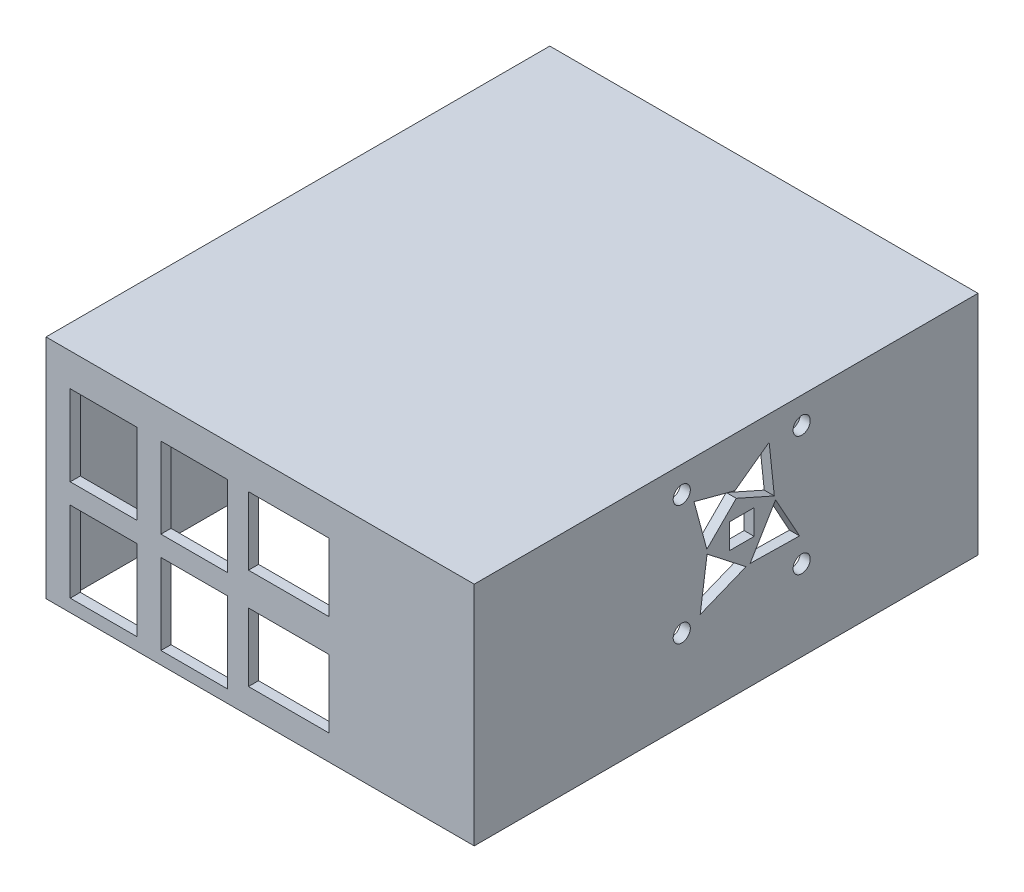
SolidWorks part; units mm, degrees
ref_plane "Front Plane" through (0, 0, 0) normal (0, 0, 1) x (1, 0, 0)
ref_plane "Top Plane" through (0, 0, 0) normal (0, 1, 0) x (1, 0, 0)
ref_plane "Right Plane" through (0, 0, 0) normal (1, 0, 0) x (0, 0, -1)
sketch "Sketch1" plane through (0, 0, 0) normal (0, 1, 0) x (1, 0, 0)
  line L1 (-42.5, -50) -> (42.5, -50)
  line L2 (-42.5, -50) -> (-42.5, 50)
  line L3 (-42.5, 50) -> (42.5, 50)
  line L4 (42.5, -50) -> (42.5, 50)
  line L5 (-42.5, -50) -> (42.5, 50) construction
  line L6 (-42.5, 50) -> (42.5, -50) construction
  point P0 (0, 0)
  dimension "D1" = 100
  dimension "D2" = 85
extrude "Boss-Extrude1" add sketch "Sketch1" along normal blind 45
shell "Shell1" thickness 2 removed face at (0, 0, 0)
sketch "Sketch3" plane through (0, 43, 0) normal (0, -1, 0) x (1, 0, 0)
  line L0 (-36.5, 24.5) -> (12.5, 24.5) construction
  line L1 (12.5, 24.5) -> (12.5, -33.5) construction
  line L2 (12.5, -33.5) -> (-36.5, -33.5) construction
  line L3 (-36.5, -33.5) -> (-36.5, 24.5) construction
  line L5 (-40.5, 48) -> (40.5, 48) construction
  line L6 (-36.5, -4.5) -> (-40.5, -4.5) construction
  line L7 (-40.5, -48) -> (-40.5, 48) construction
  line L8 (12.5, -4.5) -> (40.5, -4.5) construction
  line L9 (40.5, 48) -> (40.5, -48) construction
  circle A0 centre (-36.5, 24.5) radius 2.5
  circle A1 centre (12.5, 24.5) radius 2.5
  circle A2 centre (-36.5, -33.5) radius 2.5
  circle A3 centre (12.5, -33.5) radius 2.5
  dimension "D4" = 5
  dimension "D1" = 58
  dimension "D2" = 49
  dimension "D3" = 23.5
  dimension "D5" = 4
extrude "Boss-Extrude2" add sketch "Sketch3" along normal blind 3
sketch "Sketch4" plane through (0, 40, 0) normal (0, -1, 0) x (1, 0, 0)
  circle A0 centre (12.5, 24.5) radius 1.025
  circle A1 centre (-36.5, 24.5) radius 1.025
  circle A2 centre (-36.5, -33.5) radius 1.025
  circle A3 centre (12.5, -33.5) radius 1.025
  dimension "D1" = 2.05
extrude "Cut-Extrude1" cut sketch "Sketch4" against normal blind 2.7
sketch "Sketch17" plane through (0, 0, 50) normal (0, 0, 1) x (1, 0, 0)
  line L0 (0, 45) -> (0, 0) construction
  line L1 (-42.5, 45) -> (42.5, 45) construction
  line L2 (42.5, 38.5) -> (-42.5, 38.5) construction
  line L3 (-24.44, 22.5) -> (-37.69, 22.5)
  line L4 (-24.44, 22.5) -> (-24.44, 38.5)
  line L5 (-24.44, 38.5) -> (-37.69, 38.5)
  line L6 (-37.69, 22.5) -> (-37.69, 38.5)
  line L7 (-24.44, 22.5) -> (-37.69, 38.5) construction
  line L8 (-24.44, 38.5) -> (-37.69, 22.5) construction
  line L9 (-6.44, 22.5) -> (-19.69, 22.5)
  line L10 (-6.44, 22.5) -> (-6.44, 38.5)
  line L11 (-6.44, 38.5) -> (-19.69, 38.5)
  line L12 (-19.69, 22.5) -> (-19.69, 38.5)
  line L13 (-6.44, 22.5) -> (-19.69, 38.5) construction
  line L14 (-6.44, 38.5) -> (-19.69, 22.5) construction
  line L15 (13.69, 25) -> (-2.31, 25)
  line L16 (13.69, 25) -> (13.69, 38.5)
  line L17 (13.69, 38.5) -> (-2.31, 38.5)
  line L18 (-2.31, 25) -> (-2.31, 38.5)
  line L19 (13.69, 25) -> (-2.31, 38.5) construction
  line L20 (13.69, 38.5) -> (-2.31, 25) construction
  line L21 (42.5, 45) -> (42.5, 0) construction
  line L22 (-42.5, 45) -> (-42.5, 0) construction
  line L23 (13.69, 31.75) -> (42.5, 31.75) construction
  line L24 (-37.69, 30.5) -> (-42.5, 30.5) construction
  point P5 (-31.065, 30.5)
  point P10 (-13.065, 30.5)
  point P15 (5.69, 31.75)
  dimension "D1" = 6.5
  dimension "D2" = 13.5
  dimension "D3" = 16
  dimension "D4" = 16
  dimension "D5" = 13.25
  dimension "D6" = 4.75
  dimension "D7" = 4.13
  dimension "D8" = 4.81
extrude "Cut-Extrude2" cut sketch "Sketch17" against normal up to surface (2 mm away) up to face at (0, 21.5, 48)
pattern_linear "LPattern1" count 2 spacing 20 along (0, -1, 0) of "Cut-Extrude2"
sketch "Sketch18" plane through (42.5, 0, 0) normal (1, 0, 0) x (0, 0, -1)
  line L0 (15, 39.8) -> (-8.8, 39.8) construction
  line L1 (-2.85, 21.95) -> (0.125, 16)
  line L2 (-8.8, 39.8) -> (-8.8, 16) construction
  line L3 (-8.8, 16) -> (15, 16) construction
  line L4 (15, 16) -> (15, 39.8) construction
  line L5 (-50, 45) -> (50, 45) construction
  line L6 (50, 45) -> (50, 0) construction
  line L7 (3.1, 16) -> (3.1, 39.8) construction
  line L8 (3.1, 27.9) -> (-8.8, 27.9) construction
  line L9 (3.1, 27.9) -> (15, 27.9) construction
  line L10 (9.05, 27.9) -> (9.05, 16) construction
  line L11 (9.05, 21.95) -> (3.1, 21.95) construction
  line L12 (9.05, 21.95) -> (15, 21.95) construction
  line L13 (12.025, 16) -> (15, 21.95)
  line L14 (15, 21.95) -> (9.05, 21.95)
  line L15 (9.05, 21.95) -> (12.025, 16)
  line L22 (9.05, 21.95) -> (9.05, 16)
  line L23 (9.05, 16) -> (3.1, 18.975)
  line L24 (3.1, 18.975) -> (9.05, 21.95)
  line L25 (9.05, 21.95) -> (3.1, 21.95)
  line L26 (3.1, 21.95) -> (6.075, 27.9)
  line L27 (6.075, 27.9) -> (9.05, 21.95)
  line L28 (6.075, 21.95) -> (6.075, 27.9) construction
  line L29 (9.05, 18.975) -> (3.1, 18.975) construction
  line L30 (12.025, 16) -> (12.025, 21.95) construction
  line L31 (9.05, 21.95) -> (9.05, 27.9)
  line L32 (9.05, 27.9) -> (9.05, 21.95) construction
  line L33 (9.05, 27.9) -> (15, 24.925)
  line L34 (15, 24.925) -> (9.05, 21.95)
  line L35 (15, 24.925) -> (9.05, 24.925) construction
  line L36 (0.125, 16) -> (3.1, 21.95)
  line L37 (3.1, 21.95) -> (-2.85, 21.95)
  line L38 (0.125, 16) -> (0.125, 21.95) construction
  line L39 (-2.85, 18.975) -> (-8.8, 18.975) construction
  line L40 (-2.85, 21.95) -> (-2.85, 16)
  line L41 (-2.85, 16) -> (-8.8, 18.975)
  line L42 (-8.8, 18.975) -> (-2.85, 21.95)
  line L43 (-5.825, 21.95) -> (-5.825, 27.9) construction
  line L44 (-2.85, 21.95) -> (-8.8, 21.95)
  line L45 (-8.8, 21.95) -> (-5.825, 27.9)
  line L46 (-5.825, 27.9) -> (-2.85, 21.95)
  line L47 (3.1, 24.925) -> (-2.85, 24.925) construction
  line L48 (-2.85, 21.95) -> (-2.85, 27.9)
  line L49 (-2.85, 27.9) -> (3.1, 24.925)
  line L50 (3.1, 24.925) -> (-2.85, 21.95)
  line L51 (-2.85, 33.85) -> (0.125, 27.9)
  line L52 (0.125, 27.9) -> (3.1, 33.85)
  line L53 (3.1, 33.85) -> (-2.85, 33.85)
  line L54 (0.125, 27.9) -> (0.125, 33.85) construction
  line L55 (-2.85, 30.875) -> (-8.8, 30.875) construction
  line L56 (-2.85, 33.85) -> (-2.85, 27.9)
  line L57 (-2.85, 27.9) -> (-8.8, 30.875)
  line L58 (-8.8, 30.875) -> (-2.85, 33.85)
  line L59 (-5.825, 33.85) -> (-5.825, 39.8) construction
  line L60 (-2.85, 33.85) -> (-8.8, 33.85)
  line L61 (-8.8, 33.85) -> (-5.825, 39.8)
  line L62 (-5.825, 39.8) -> (-2.85, 33.85)
  line L63 (3.1, 36.825) -> (-2.85, 36.825) construction
  line L64 (-2.85, 33.85) -> (-2.85, 39.8)
  line L65 (-2.85, 39.8) -> (3.1, 36.825)
  line L66 (3.1, 36.825) -> (-2.85, 33.85)
  line L67 (9.05, 33.85) -> (12.025, 27.9)
  line L68 (12.025, 27.9) -> (15, 33.85)
  line L69 (15, 33.85) -> (9.05, 33.85)
  line L70 (12.025, 27.9) -> (12.025, 33.85) construction
  line L71 (9.05, 30.875) -> (3.1, 30.875) construction
  line L72 (9.05, 33.85) -> (9.05, 27.9)
  line L73 (9.05, 27.9) -> (3.1, 30.875)
  line L74 (3.1, 30.875) -> (9.05, 33.85)
  line L75 (6.075, 33.85) -> (6.075, 39.8) construction
  line L76 (9.05, 33.85) -> (3.1, 33.85)
  line L77 (3.1, 33.85) -> (6.075, 39.8)
  line L78 (6.075, 39.8) -> (9.05, 33.85)
  line L79 (15, 36.825) -> (9.05, 36.825) construction
  line L80 (9.05, 33.85) -> (9.05, 39.8)
  line L81 (9.05, 39.8) -> (15, 36.825)
  line L82 (15, 36.825) -> (9.05, 33.85)
  line L83 (-8.8, 21.95) -> (-8.8, 30.875)
  line L84 (-8.8, 30.875) -> (-8.8, 33.85)
  line L85 (-2.85, 39.8) -> (-5.825, 39.8)
  line L86 (-2.85, 39.8) -> (3.1, 39.8)
  line L87 (3.1, 39.8) -> (6.075, 39.8)
  line L88 (9.05, 39.8) -> (6.075, 39.8)
  line L89 (15, 36.825) -> (15, 33.85)
  line L90 (15, 27.9) -> (15, 33.85)
  line L91 (15, 21.95) -> (15, 27.9)
  line L92 (12.025, 16) -> (9.05, 16)
  line L93 (9.05, 16) -> (3.1, 16)
  line L94 (3.1, 16) -> (0.125, 16)
  line L95 (0.125, 16) -> (-2.85, 16)
  line L96 (-8.8, 21.95) -> (-8.8, 18.975)
  circle A0 centre (15, 39.8) radius 1.7
  circle A1 centre (-8.8, 39.8) radius 1.7
  circle A2 centre (-8.8, 16) radius 1.7
  circle A3 centre (15, 16) radius 1.7
  dimension "D1" = 3.4
  dimension "D2" = 23.8
  dimension "D3" = 5.2
  dimension "D4" = 35
  dimension "D5" = 2
  dimension "D6" = 2
extrude "Cut-Extrude3" cut sketch "Sketch18" against normal up to surface (2 mm away) contours A3 | A2 | A1 | A0 region at (42.5, 39.8, -15) region at (42.5, 39.8, 8.8) region at (42.5, 16, 8.8) region at (42.5, 16, -15) up to face at (40.5, 21.5, 0)
sketch "Sketch19" plane through (42.5, 0, 0) normal (1, 0, 0) x (0, 0, -1)
  line L0 (-8.8, 41.5) -> (-8.8, 14.3) construction
  line L1 (-8.8, 14.3) -> (15, 14.3) construction
  line L2 (15, 14.3) -> (15, 41.5) construction
  line L3 (15, 41.5) -> (13.3, 41.5) construction
  line L4 (-8.8, 41.5) -> (15, 41.5) construction
  line L5 (3.1, 41.5) -> (3.1, 14.3) construction
  line L6 (-8.8, 27.9) -> (15, 27.9) construction
  line L7 (3.1, 34.8282) -> (10.0282, 27.9)
  line L8 (10.0282, 27.9) -> (12.5641, 37.3641)
  line L9 (12.5641, 37.3641) -> (3.1, 34.8282)
  line L10 (12.5641, 37.3641) -> (6.5641, 31.3641) construction
  line L11 (3.1, 34.8282) -> (3.1, 27.9) construction
  line L12 (3.1, 27.9) -> (10.0282, 27.9) construction
  line L13 (3.1, 27.9) -> (6.5641, 31.3641) construction
  line L14 (3.1, 34.8282) -> (-6.3641, 37.3641)
  line L15 (-6.3641, 37.3641) -> (-3.8282, 27.9)
  line L16 (-3.8282, 27.9) -> (3.1, 34.8282)
  line L17 (-6.3641, 37.3641) -> (-0.3641, 31.3641) construction
  line L18 (-0.3641, 31.3641) -> (3.1, 27.9) construction
  line L22 (-3.8282, 27.9) -> (-6.3641, 18.4359)
  line L23 (-6.3641, 18.4359) -> (3.1, 20.9718)
  line L24 (3.1, 20.9718) -> (-3.8282, 27.9)
  line L25 (-0.3641, 24.4359) -> (3.1, 27.9) construction
  line L26 (-0.3641, 24.4359) -> (-6.3641, 18.4359) construction
  line L27 (3.1, 20.9718) -> (10.0282, 27.9)
  line L28 (10.0282, 27.9) -> (12.5641, 18.4359)
  line L29 (12.5641, 18.4359) -> (3.1, 20.9718)
  line L30 (12.5641, 18.4359) -> (6.5641, 24.4359) construction
  line L31 (6.5641, 24.4359) -> (3.1, 27.9) construction
  line L33 (0.6251, 25.4251) -> (5.5749, 25.4251)
  line L34 (0.6251, 25.4251) -> (0.6251, 30.3749)
  line L35 (0.6251, 30.3749) -> (5.5749, 30.3749)
  line L36 (5.5749, 25.4251) -> (5.5749, 30.3749)
  line L37 (0.6251, 25.4251) -> (5.5749, 30.3749) construction
  line L38 (0.6251, 30.3749) -> (5.5749, 25.4251) construction
  circle A0 centre (-8.8, 39.8) radius 1.7 construction
  circle A1 centre (-8.8, 16) radius 1.7 construction
  circle A2 centre (15, 16) radius 1.7 construction
  circle A3 centre (15, 39.8) radius 1.7 construction
  point P38 (0, 0)
  point P39 (0, 0)
  dimension "D1" = 6
  dimension "D2" = 45
  dimension "D3" = 45
  dimension "D4" = 7
extrude "Cut-Extrude9" cut sketch "Sketch19" against normal blind 10 contours L15 L16 L14 region at (42.5, 33.3641, 2.3641)
ref_axis "Axis1" through (42.5, 27.9, -3.1) along (1, 0, 0)
pattern_circular "CirPattern2" count 4 every 97 about axis through (42.5, 27.9, -3.1) along (1, 0, 0) of "Cut-Extrude9"
extrude "Cut-Extrude10" cut sketch "Sketch19<4>" against normal blind 10 contours L33 L36 L35 L34 region at (42.5, 27.9, -3.1)
sketch "Sketch19<4>" plane through (42.5, 0, 0) normal (1, 0, 0) x (0, 0, -1) same geometry as "Sketch19"
